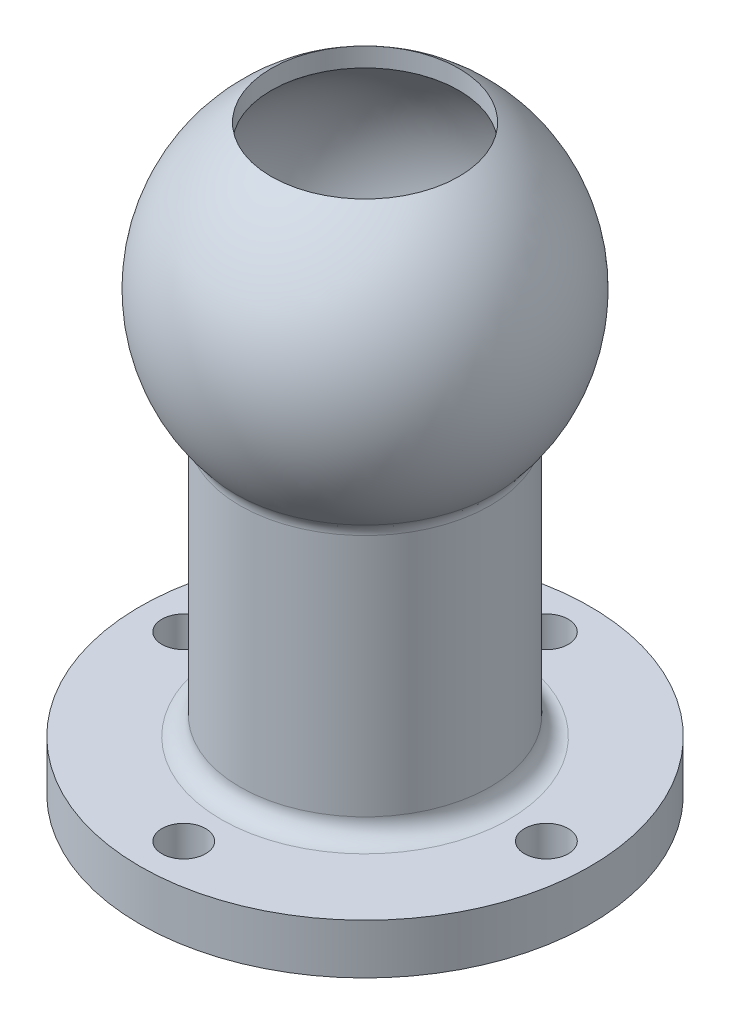
SolidWorks part; units mm, degrees
ref_plane "Ön Düzlem" through (0, 0, 0) normal (0, 0, 1) x (1, 0, 0)
ref_plane "Üst Düzlem" through (0, 0, 0) normal (0, 1, 0) x (1, 0, 0)
ref_plane "Sağ Düzlem" through (0, 0, 0) normal (1, 0, 0) x (0, 0, -1)
sketch "Çizim1" plane through (0, 0, 0) normal (0, 1, 0) x (1, 0, 0)
  circle A0 centre (0, 0) radius 36
  dimension "D1" = 72
extrude "Yükseklik-Ekstrüzyon1" add sketch "Çizim1" along normal blind 8
sketch "Çizim2" plane through (0, 8, 0) normal (0, 1, 0) x (1, 0, 0)
  line L0 (0, 0) -> (0, 36) construction
  circle A0 centre (0, 0) radius 36 construction
  circle A1 centre (0, 0) radius 29 construction
  circle A2 centre (0, 29) radius 3.5
  circle A3 centre (29, 0) radius 3.5
  circle A4 centre (0, -29) radius 3.5
  circle A5 centre (-29, 0) radius 3.5
  point P8 (0, 0)
  point P9 (-29, 0)
  point P17 (0, 0)
  dimension "D1" = 58
  dimension "D2" = 7
  dimension "D3" = 4
extrude "Kes-Ekstrüzyon1" cut sketch "Çizim2" against normal blind 8
sketch "Çizim3" plane through (0, 0, 0) normal (0, -1, 0) x (1, 0, 0)
  circle A0 centre (0, 0) radius 17.5
  dimension "D1" = 35
extrude "Kes-Ekstrüzyon2" cut sketch "Çizim3" against normal blind 2
sketch "Çizim4" plane through (0, 0, 0) normal (1, 0, 0) x (0, 0, -1)
  line L0 (0, 0) -> (0, 45.3394) construction
  line L1 (20, 8) -> (20, 37)
  line L2 (36, 8) -> (-36, 8) construction
  line L3 (20, 8) -> (0, 8)
  line L4 (20, 37) -> (0, 37)
  line L5 (0, 37) -> (0, 8)
  dimension "D1" = 20
  dimension "D2" = 29
revolve "Döndür1" add sketch "Çizim4" angle 360 about L5
ref_plane "Düzlem1" through (0, 8, 0) normal (0, 1, 0) x (1, 0, 0)
sketch "Çizim5" plane through (0, 8, 0) normal (0, 1, 0) x (1, 0, 0)
  circle A0 centre (0, 0) radius 15
  dimension "D1" = 30
extrude "Kes-Ekstrüzyon3" cut sketch "Çizim5" along normal blind 29 and the other way blind 6
ref_plane "Düzlem2" through (0, 37, 0) normal (0, 1, 0) x (1, 0, 0)
sketch "Çizim6" plane through (0, 37, 0) normal (0, 1, 0) x (1, 0, 0)
  circle A0 centre (0, 0) radius 20
  dimension "D1" = 40
extrude "Yükseklik-Ekstrüzyon2" add sketch "Çizim6" along normal blind 3
sketch "Çizim8" plane through (0, 37, 0) normal (0, -1, 0) x (1, 0, 0)
  circle A0 centre (0, 0) radius 12.5
  dimension "D1" = 25
extrude "Kes-Ekstrüzyon4" cut sketch "Çizim8" against normal blind 3
ref_plane "Düzlem3" through (0, 40, 0) normal (0, 1, 0) x (1, 0, 0)
sketch "Çizim10" plane through (0, 0, 0) normal (0, 0, 1) x (1, 0, 0)
  line L0 (20, 40) -> (-20, 40) construction
  line L1 (0, 97.5) -> (0, 42.5) construction
  line L2 (-20, 40) -> (-20, 51.1254)
  line L3 (0, 45) -> (0, 40)
  line L4 (20, 40) -> (-20, 40)
  arc A0 (0, 97.5) -> (0, 42.5) centre (0, 70) ccw
  arc A2 (0, 95) -> (0, 45) centre (0, 70) ccw
  point P13 (0, 40)
  dimension "D2" = 55
  dimension "D3" = 50
  dimension "D1" = 70
  dimension "D4" = 30
revolve "Döndür15" add sketch "Çizim10" angle 360 about L1 region at (-0.6149, 96.25, 0)
revolve "Döndür17" add sketch "Çizim10<16>" angle 360 about L1 region at (-12.6686, 43.1851, 0)
sketch "Çizim10<16>" plane through (0, 0, 0) normal (0, 0, 1) x (1, 0, 0) same geometry as "Çizim10"
sketch "Çizim13" plane through (0, 40, 0) normal (0, -1, 0) x (1, 0, 0)
  circle A0 centre (0, 0) radius 15
  dimension "D1" = 30
extrude "Kes-Ekstrüzyon5" cut sketch "Çizim13" against normal blind 65
fillet "Radyus2" radius 3 1 edges at (0, 51.1254, 20)
fillet "Radyus3" radius 3 1 edges at (0, 40, -15)
fillet "Radyus4" radius 3 1 edges at (0, 8, 20)
